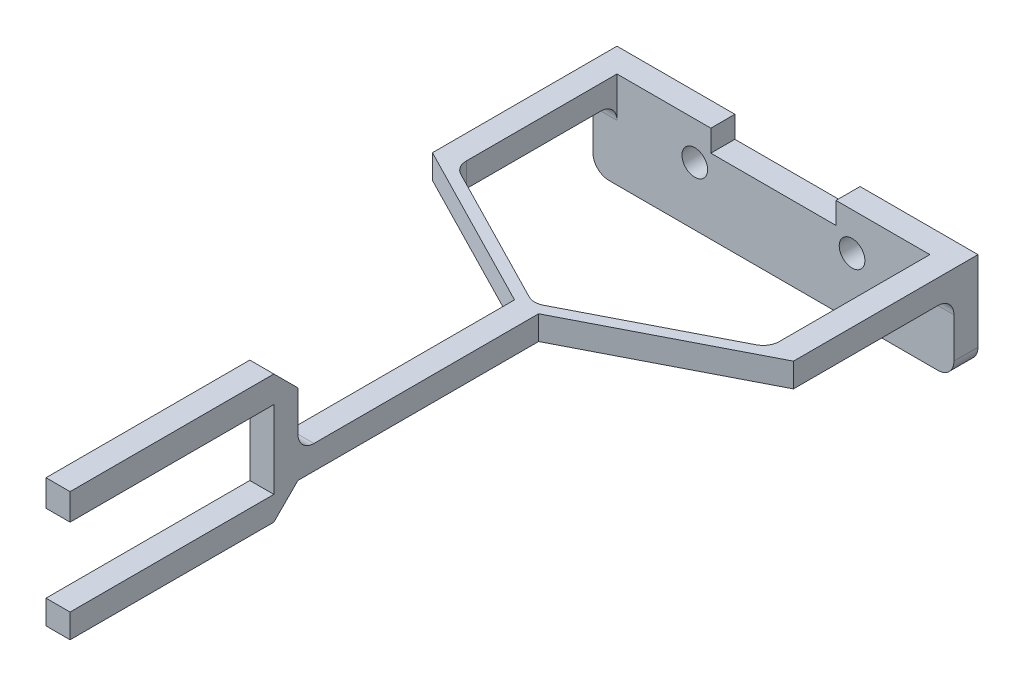
SolidWorks part; units mm, degrees
ref_plane "Front Plane" through (0, 0, 0) normal (0, 0, 1) x (1, 0, 0)
ref_plane "Top Plane" through (0, 0, 0) normal (0, 1, 0) x (1, 0, 0)
ref_plane "Right Plane" through (0, 0, 0) normal (1, 0, 0) x (0, 0, -1)
sketch "Sketch1" plane through (0, 0, 0) normal (0, 0, 1) x (1, 0, 0)
  line L1 (-22.5, 6) -> (22.5, 6)
  line L2 (-22.5, 6) -> (-22.5, -6)
  line L3 (-22.5, -6) -> (22.5, -6)
  line L4 (22.5, 6) -> (22.5, -6)
  line L5 (-22.5, 6) -> (22.5, -6) construction
  line L6 (-22.5, -6) -> (22.5, 6) construction
  point P0 (0, 0)
  dimension "D1" = 12
  dimension "D2" = 45
extrude "Boss-Extrude1" add sketch "Sketch1" along normal blind 3
sketch "Sketch2" plane through (0, 0, 3) normal (0, 0, 1) x (1, 0, 0)
  line L0 (-22.5, -6) -> (22.5, -6) construction
  line L1 (-22.5, 6) -> (-19.5, 6)
  line L2 (-22.5, 6) -> (-22.5, -6)
  line L3 (-22.5, -6) -> (-19.5, -6)
  line L4 (-19.5, 6) -> (-19.5, -6)
  line L6 (22.5, 6) -> (19.5, 6)
  line L7 (22.5, 6) -> (22.5, -6)
  line L8 (22.5, -6) -> (19.5, -6)
  line L9 (19.5, 6) -> (19.5, -6)
  dimension "D1" = 3
extrude "Boss-Extrude2" add sketch "Sketch2" along normal blind 20
sketch "Sketch3" plane through (0, 6, 0) normal (0, 1, 0) x (1, 0, 0)
  line L0 (-19.5, -23) -> (0, -33)
  line L1 (0, -33) -> (19.5, -23)
  line L2 (-19.5, -23) -> (-22.5, -23)
  line L3 (-22.5, -23) -> (-1.5, -33.7692)
  line L4 (1.5, -33.7692) -> (22.5, -23)
  line L5 (22.5, -23) -> (19.5, -23)
  line L6 (-19.5, -23) -> (19.5, -23) construction
  line L10 (-1.5, -33.7692) -> (-1.5, -63.7692)
  line L11 (-1.5, -63.7692) -> (1.5, -63.7692)
  line L12 (1.5, -63.7692) -> (1.5, -33.7692)
  point P11 (0, 0)
  point P12 (0, 0)
  point P13 (0, -33)
  point P14 (0, -40.7718)
  dimension "D1" = 3
  dimension "D2" = 30
  dimension "D3" = 10
extrude "Boss-Extrude3" add sketch "Sketch3" against normal up to surface (12 mm away) up to face at (0, -6, 12.25)
sketch "Sketch4" plane through (1.5, 0, 0) normal (1, 0, 0) x (0, 0, -1)
  line L0 (-33.7692, -6) -> (-33.7692, 6) construction
  line L1 (-66, 3) -> (-33.7692, 3)
  line L2 (-66, 3) -> (-66, -6)
  line L3 (-66, -6) -> (-33.7692, -6)
  line L4 (-33.7692, 3) -> (-33.7692, -6)
  line L5 (-33.7692, -6) -> (-63.7692, -6) construction
  line L6 (-63.7692, 6) -> (-33.7692, 6) construction
  dimension "D1" = 3
extrude "Cut-Extrude3" cut sketch "Sketch4" against normal up to surface (3 mm away) up to face at (-1.5, 0, 48.7692)
sketch "Sketch5" plane through (1.5, 0, 0) normal (1, 0, 0) x (0, 0, -1)
  line L1 (-3, -6) -> (-33.7692, -6)
  line L2 (-33.7692, -6) -> (-33.7692, 3)
  line L3 (-33.7692, 3) -> (-3, 3)
  line L4 (-3, 3) -> (-3, -6)
  line L5 (0, -6) -> (0, 6) construction
  dimension "D1" = 3
extrude "Cut-Extrude4" cut sketch "Sketch5" against normal up to surface and the other way up to surface up to face at (-22.5, 0, 11.5) other way up to face at (22.5, 0, 11.5)
sketch "Sketch8" plane through (-1.5, 0, 0) normal (-1, 0, 0) x (0, 0, 1)
  line L1 (63.7692, 0) -> (92.1692, 0)
  line L2 (92.1692, 0) -> (92.1692, 3)
  line L3 (92.1692, 3) -> (66.7692, 3)
  line L4 (66.7692, 3) -> (66.7692, 12.7)
  line L5 (66.7692, 12.7) -> (92.1692, 12.7)
  line L6 (92.1692, 12.7) -> (92.1692, 16)
  line L7 (92.1692, 16) -> (85.7417, 16)
  line L8 (63.7692, 3) -> (63.7692, 6) construction
  line L9 (63.7692, 0) -> (63.7692, 3)
  line L10 (63.7692, 16) -> (85.7417, 16)
  line L14 (63.7692, 3) -> (63.7692, 6)
  line L15 (63.7692, 6) -> (63.7692, 16)
  dimension "D1" = 3
  dimension "D2" = 10
  dimension "D3" = 25.4
  dimension "D4" = 9.7
  dimension "D5" = 3
extrude "Boss-Extrude6" add sketch "Sketch8" against normal up to surface (3 mm away) up to face at (1.5, 4.5, 48.7692)
chamfer "Chamfer4" distance 3 angle 45 1 edges at (0, 16, 63.7692)
chamfer "Chamfer5" distance 3 angle 45 1 edges at (0, 0, 63.7692)
sketch "Sketch9" plane through (0, 0, 0) normal (0, 0, -1) x (-1, 0, 0)
  line L0 (-22.5, 6) -> (22.5, 6) construction
  line L1 (7.8, 3.298) -> (-7.8, 3.298)
  line L2 (7.8, 3.298) -> (7.8, 8.702)
  line L3 (7.8, 8.702) -> (-7.8, 8.702)
  line L4 (-7.8, 3.298) -> (-7.8, 8.702)
  line L5 (7.8, 3.298) -> (-7.8, 8.702) construction
  line L6 (7.8, 8.702) -> (-7.8, 3.298) construction
  point P0 (0, 6)
  dimension "D1" = 15.6
extrude "Cut-Extrude5" cut sketch "Sketch9" against normal up to surface (3 mm away) up to face at (0, 1.5, 3)
sketch "Sketch10" plane through (0, 0, 0) normal (0, 0, -1) x (-1, 0, 0)
  line L0 (0, 7.9945) -> (0, -8.0213) construction
  line L2 (-8.2, 1.298) -> (-8.2, -8.5783) construction
  line L4 (-9.8, 2.898) -> (-4.7669, 2.898) construction
  circle A0 centre (-9.8, 1.298) radius 1.6
  circle A1 centre (9.8, 1.298) radius 1.6
  dimension "D1" = 3.2
  dimension "D2" = 2
  dimension "D3" = 2
extrude "Cut-Extrude6" cut sketch "Sketch10" against normal up to surface (3 mm away) up to face at (0, 2.5497, 3)
fillet "Fillet1" radius 2 4 edges at (0, 6, 63.7692) (19.5, 4.5, 23) (0, 4.5, 33) (-19.5, 4.5, 23)
fillet "Fillet2" radius 2 2 edges at (-21, 3, 3) (21, 3, 3)
fillet "Fillet3" radius 2 2 edges at (22.5, -6, 1.5) (-22.5, -6, 1.5)
